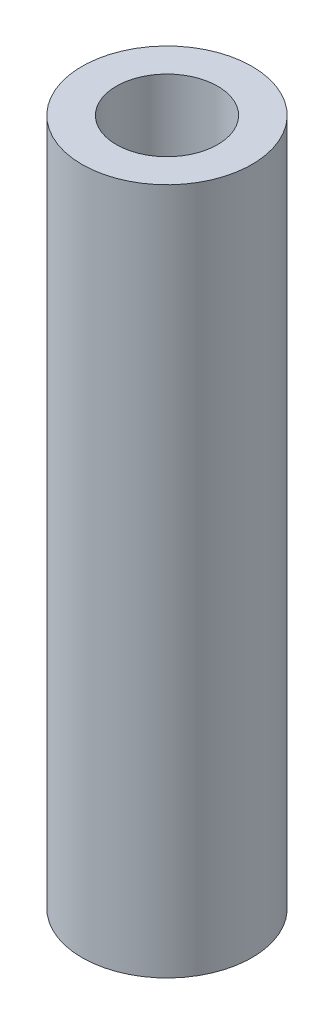
SolidWorks part; units mm, degrees
ref_plane "Front Plane" through (0, 0, 0) normal (0, 0, 1) x (1, 0, 0)
ref_plane "Top Plane" through (0, 0, 0) normal (0, 1, 0) x (1, 0, 0)
ref_plane "Right Plane" through (0, 0, 0) normal (1, 0, 0) x (0, 0, -1)
sketch "Sketch1" plane through (0, 0, 0) normal (0, 1, 0) x (1, 0, 0)
  circle A0 centre (0, 0) radius 2.475
  circle A1 centre (0, 0) radius 1.475
  dimension "D1" = 2.95
  dimension "D2" = 1
extrude "Boss-Extrude1" add sketch "Sketch1" along normal blind 20 contours A0 A1 region at (-2.405, 0, 0)
equation "\"TABH\"=2.95"
equation "\"D1@Sketch1\"=\"TABH\""
equation "\"T\"=1"
equation "\"D2@Sketch1\"=\"T\""
equation "\"H\"=20"
equation "\"D1@Boss-Extrude1\"=\"H\""
